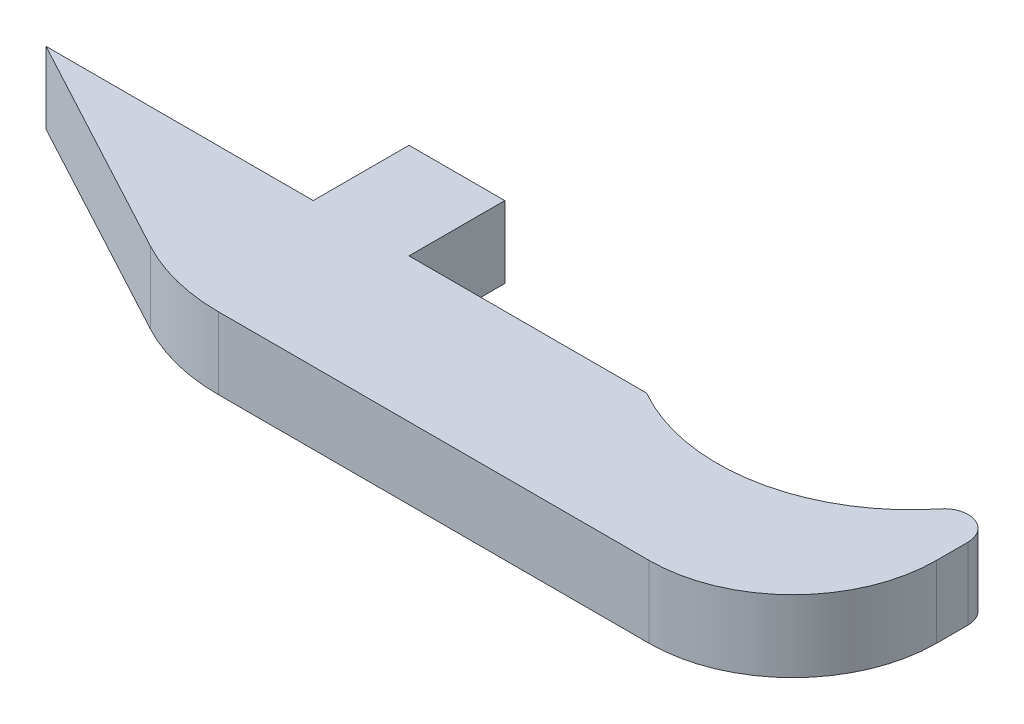
SolidWorks part; units mm, degrees
material "AISI 4130 Steel, annealed at 865C"
ref_plane "X-Y Datum" through (0, 0, 0) normal (0, 0, 1) x (1, 0, 0)
ref_plane "X-Z Datum" through (0, 0, 0) normal (0, 1, 0) x (1, 0, 0)
ref_plane "Y-Z Datum" through (0, 0, 0) normal (1, 0, 0) x (0, 0, -1)
sketch "Sketch1" plane through (0, 0, 0) normal (0, 1, 0) x (1, 0, 0)
  line L0 (20.8895, 0) -> (0, 0) construction
  line L1 (49.3776, 0) -> (0, 0)
  line L2 (49.3776, 0) -> (49.3776, 11.1252)
  line L3 (20.9296, -9.525) -> (62.2046, -9.525)
  line L4 (62.2046, 11.1252) -> (62.2046, -9.525)
  line L5 (3.175, 0) -> (20.9296, -9.525)
  circle A0 centre (49.3776, 11.1252) radius 12.827
  dimension "D3" = 25.654
  dimension "D5" = 9.525
  dimension "D1" = 49.3776
  dimension "D2" = 11.1252
  dimension "D4" = 3.175
  dimension "D6" = 41.275
extrude "Boss-Extrude1" add sketch "Sketch1" along normal blind 4.7625 contours L1 A0 region at (37.4995, 0, 4.291)
fillet "Fillet1" radius 9.525 1 edges at (62.2046, 2.3813, 9.525)
fillet "Fillet2" radius 1.5875 1 edges at (62.2046, 2.3813, -11.1252)
fillet "Fillet4" radius 12.7 1 edges at (20.9296, 2.3813, 9.525)
sketch "Sketch2" plane through (0, 0, 0) normal (0, -1, 0) x (1, 0, 0)
  line L1 (27.2395, -6.35) -> (27.2395, 0)
  line L2 (-7.0505, -6.35) -> (27.8745, -6.35) construction
  line L3 (27.2395, 0) -> (20.8895, 0)
  line L4 (27.2395, 0) -> (27.2395, -6.35)
  line L5 (27.2395, -6.35) -> (20.8895, -6.35)
  line L6 (20.8895, 0) -> (20.8895, -6.35)
  line L7 (33.5895, 0) -> (33.5895, -6.35) construction
  line M6 (3.175, 0) -> (42.9931, 0)
  dimension "D1" = 6.35
  dimension "D2" = 6.35
extrude "Boss-Extrude2" add sketch "Sketch2" against normal blind 4.7625 contours L6 L5 L1 M6 region at (24.0645, 0, -3.175)
